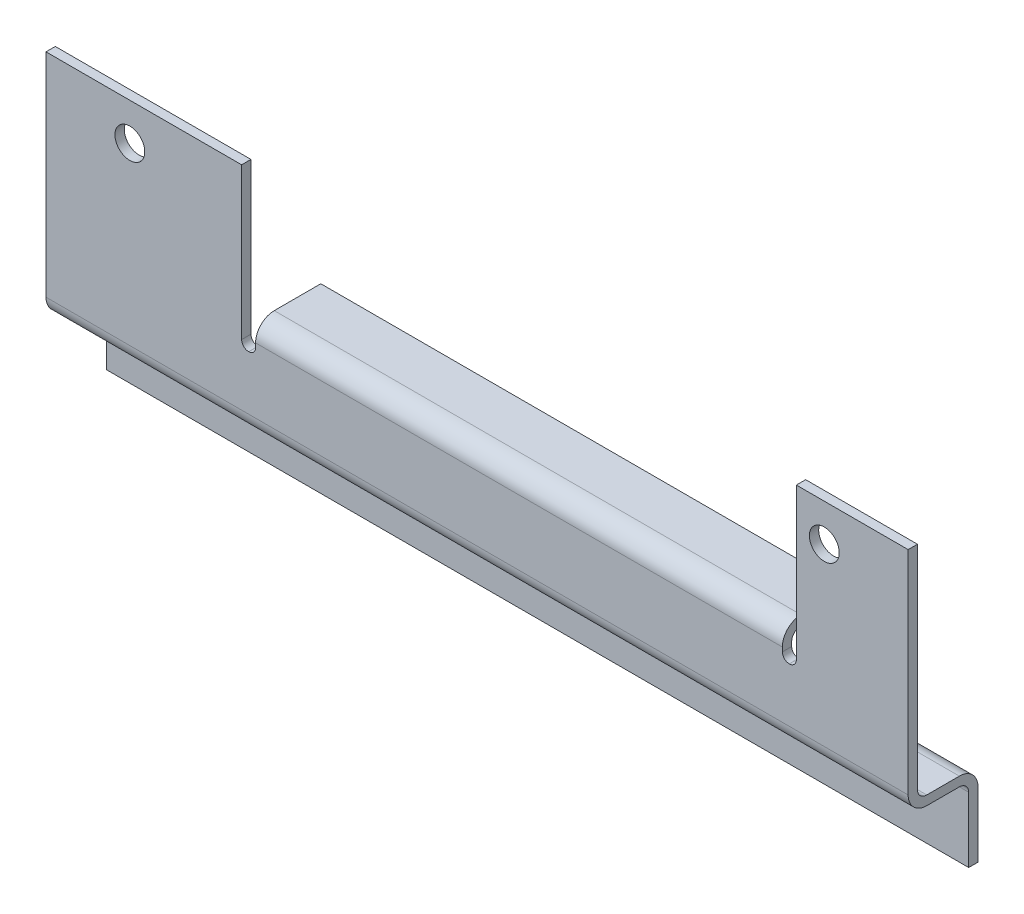
SolidWorks part; units mm, degrees
ref_plane "Face" through (0, 0, 0) normal (0, 0, 1) x (1, 0, 0)
ref_plane "Dessus" through (0, 0, 0) normal (0, 1, 0) x (1, 0, 0)
ref_plane "Droite" through (0, 0, 0) normal (1, 0, 0) x (0, 0, -1)
sketch "Esquisse1" plane through (0, 0, 0) normal (0, 0, 1) x (1, 0, 0)
  line L0 (-46.275, -25.41) -> (-25.275, -25.41)
  line L1 (46.275, -25.41) -> (46.275, -49.22)
  line L3 (-46.275, -25.41) -> (-46.275, -49.22)
  line L5 (34.275, -25.41) -> (34.275, -39.22)
  line L6 (-25.275, -25.41) -> (-25.275, -39.22)
  line L7 (34.275, -25.41) -> (46.275, -25.41)
  line L8 (-25.275, -39.22) -> (34.275, -39.22)
  line L10 (-46.275, -49.22) -> (46.275, -49.22)
  circle A1 centre (37.275, -29.41) radius 1.6
  circle A2 centre (-37.275, -29.41) radius 1.6
  dimension "D1" = 25.41
  dimension "D6" = 46.275
  dimension "D2" = 12
  dimension "D3" = 21
  dimension "D4" = 13.81
  dimension "D5" = 10
  dimension "D7" = 4
  dimension "D8" = 9
  dimension "D9" = 9
  dimension "D10" = 4
extrude "Extrusion1" add sketch "Esquisse1" along normal blind 1
sketch "Esquisse2" plane through (0, 0, 1) normal (0, 0, 1) x (1, 0, 0)
  line L1 (-25.275, -39.22) -> (34.275, -39.22)
  line L2 (-25.275, -39.22) -> (-25.275, -40.22)
  line L3 (-25.275, -40.22) -> (34.275, -40.22)
  line L4 (34.275, -39.22) -> (34.275, -40.22)
  dimension "D1" = 1
extrude "Extrusion2" add sketch "Esquisse2" against normal blind 7
sketch "Esquisse3" plane through (0, 0, 1) normal (0, 0, 1) x (1, 0, 0)
  line L1 (-46.275, -49.22) -> (46.275, -49.22)
  line L2 (-46.275, -49.22) -> (-46.275, -50.22)
  line L3 (-46.275, -50.22) -> (46.275, -50.22)
  line L4 (46.275, -49.22) -> (46.275, -50.22)
  dimension "D1" = 1
extrude "Extrusion3" add sketch "Esquisse3" against normal blind 7.5
sketch "Esquisse4" plane through (0, -50.22, 0) normal (0, -1, 0) x (1, 0, 0)
  line L0 (46.275, -6.5) -> (46.275, 1) construction
  line L1 (-46.275, -6.5) -> (46.275, -6.5)
  line L2 (-46.275, -6.5) -> (-46.275, -5.5)
  line L3 (-46.275, -5.5) -> (46.275, -5.5)
  line L4 (46.275, -6.5) -> (46.275, -5.5)
  dimension "D1" = 1
extrude "Extrusion4" add sketch "Esquisse4" along normal blind 8
fillet "Congé1" radius 1 2 edges
fillet "Congé2" radius 2 2 edges at (0, -49.22, -6.5) (0, -50.22, 1)
fillet "Congé3" radius 1 1 edges at (4.5, -40.22, 0)
fillet "Congé4" radius 2 1 edges at (4.5, -39.22, 1)
sketch "Esquisse5" plane through (0, 0, 1) normal (0, 0, 1) x (1, 0, 0)
  line L0 (-25.275, -25.41) -> (-25.275, -42.41)
  line L1 (34.275, -25.41) -> (34.275, -42.41)
  line L2 (-23.775, -25.41) -> (-23.775, -42.41)
  line L3 (32.775, -25.41) -> (32.775, -42.41)
  line L4 (-25.275, -42.41) -> (-23.775, -42.41)
  line L5 (32.775, -42.41) -> (34.275, -42.41)
  line L6 (-25.275, -25.41) -> (-23.775, -25.41)
  line L7 (32.775, -25.41) -> (34.275, -25.41)
  dimension "D1" = 1.5
  dimension "D2" = 1.5
extrude "Enlèv. mat.-Extru.1" cut sketch "Esquisse5" against normal blind 10
fillet "Congé5" radius 0.75 1 edges at (-25.275, -42.41, 0.5)
fillet "Congé6" radius 0.74 1 edges at (-23.775, -42.41, 0.5)
fillet "Congé7" radius 0.74 1 edges at (32.775, -42.41, 0.5)
fillet "Congé8" radius 0.75 1 edges at (34.275, -42.41, 0.5)
